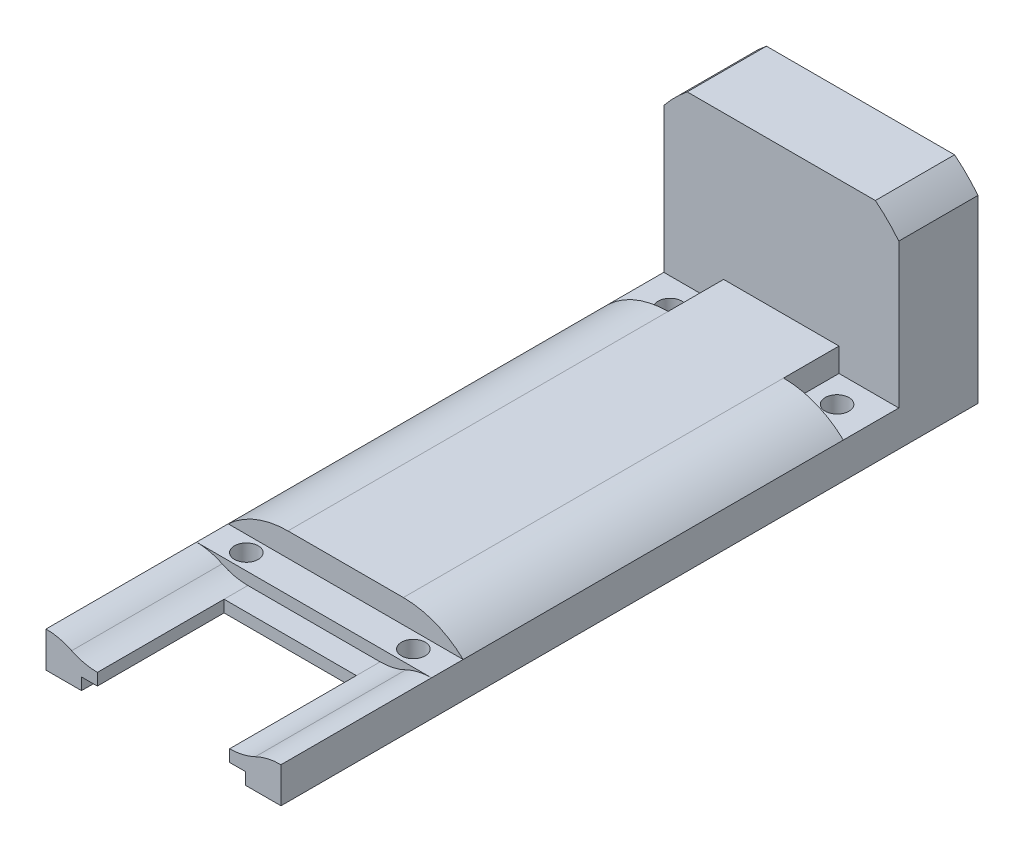
SolidWorks part; units mm, degrees
ref_plane "Front Plane" through (0, 0, 0) normal (0, 0, 1) x (1, 0, 0)
ref_plane "Top Plane" through (0, 0, 0) normal (0, 1, 0) x (1, 0, 0)
ref_plane "Right Plane" through (0, 0, 0) normal (1, 0, 0) x (0, 0, -1)
sketch "Sketch1" plane through (0, 0, 0) normal (0, 0, 1) x (1, 0, 0)
  line L0 (0, 0) -> (0, 29.3495) construction
  line L1 (-14.835, 0) -> (-8.35, 0)
  line L4 (-14.835, 0) -> (-14.835, 4.5)
  line L5 (-14.835, 4.5) -> (-8.35, 4.5)
  line L6 (14.835, 0) -> (14.835, 4.5)
  line L7 (14.835, 0) -> (8.35, 0)
  line L11 (8.35, 4.5) -> (14.835, 4.5)
  line L12 (-8.35, 4.5) -> (8.35, 4.5) construction
  line L13 (-8.35, 0) -> (8.35, 0) construction
  line L14 (-8.35, 0) -> (-8.35, 4.5)
  line L15 (8.35, 0) -> (8.35, 4.5)
  point P10 (0, 21.4888)
  point P13 (0, 23.4888)
  point P16 (0, 0)
  dimension "D1" = 29.67
  dimension "D2" = 6.485
  dimension "D4" = 4.5
extrude "Boss-Extrude1" add sketch "Sketch1" against normal blind 88 contours L14 L5 L4 L1 | L15 L11 L6 L7
sketch "Sketch3" plane through (0, 0, 0) normal (0, 0, 1) x (1, 0, 0)
  line L0 (-14.835, 0) -> (-8.35, 0) construction
  line L1 (-8.35, 0) -> (-10.35, 0)
  line L2 (-8.35, 0) -> (-8.35, 1.5)
  line L3 (-8.35, 1.5) -> (-10.35, 1.5)
  line L4 (-10.35, 0) -> (-10.35, 1.5)
  line L5 (0, 0) -> (0, 11.8528) construction
  line L6 (8.35, 1.5) -> (10.35, 1.5)
  line L7 (10.35, 0) -> (10.35, 1.5)
  line L8 (8.35, 0) -> (10.35, 0)
  line L9 (8.35, 0) -> (8.35, 1.5)
  dimension "D1" = 2
  dimension "D2" = 1.5
extrude "Cut-Extrude2" cut sketch "Sketch3" against normal blind 30
sketch "Sketch4" plane through (0, 0, -88) normal (0, 0, -1) x (-1, 0, 0)
  line L0 (0, 0) -> (0, 13.5394) construction
  line L1 (14.835, 4.5) -> (8.35, 4.5) construction
  line L2 (8.35, 0) -> (8.35, 4.5) construction
  line L3 (8.35, 4.5) -> (10.35, 4.5)
  line L4 (-8.35, 4.5) -> (-8.35, 0)
  line L5 (8.35, 1.5) -> (8.35, 0)
  line L6 (10.35, 1.5) -> (8.35, 1.5)
  line L7 (10.35, 0) -> (10.35, 1.5)
  line L8 (8.35, 0) -> (10.35, 0)
  line L9 (8.35, 4.5) -> (8.35, 0)
  line L11 (10.35, 0) -> (10.35, 4.5)
  line L12 (8.35, 0) -> (10.35, 0)
  line L13 (-8.35, 0) -> (-10.35, 0)
  line L14 (-10.35, 0) -> (-10.35, 4.5)
  line L15 (-8.35, 4.5) -> (-10.35, 4.5)
  dimension "D1" = 0
extrude "Cut-Extrude3" cut sketch "Sketch4" against normal blind 65
sketch "Sketch6" plane through (-10.35, 0, 0) normal (1, 0, 0) x (0, 0, -1)
  line L0 (23, 4.5) -> (0, 4.5) construction
  line L1 (83, 1.5) -> (16, 1.5)
  line L2 (83, 1.5) -> (83, 4.5)
  line L3 (83, 4.5) -> (16, 4.5)
  line L4 (16, 1.5) -> (16, 4.5)
  line L6 (23, 1.5) -> (0, 1.5) construction
  dimension "D1" = 67
extrude "Boss-Extrude2" add sketch "Sketch6" along normal up to surface (20.7 mm away) up to face at (10.35, 2, -37)
sketch "Sketch8" plane through (0, 0, -88) normal (0, 0, -1) x (-1, 0, 0)
  line L0 (-14.835, 0) -> (-14.835, 4.5) construction
  line L3 (-14.835, 0) -> (-14.835, 25.7077)
  line L4 (-14.835, 25.7077) -> (14.835, 25.7077)
  line L6 (-10.35, 1.5) -> (10.35, 1.5) construction
  line L8 (0, 0) -> (0, 41.6063) construction
  line L10 (-10.35, 0) -> (-10.35, 21.2227)
  line L11 (14.835, 0) -> (14.835, 25.7077)
  line L12 (10.35, 0) -> (14.8327, 0)
  line L13 (-14.835, 0) -> (-10.35, 0)
  line L14 (-10.35, 21.2227) -> (10.35, 21.2227)
  line L15 (10.35, 21.2227) -> (10.35, 0)
  arc A1 (14.8327, 22.748) -> (11.874, 25.7067) centre (0, 10.874) ccw construction
  point P26 (0, 25.7077)
  dimension "D1" = 24.2077
  dimension "D2" = 4.485
extrude "Boss-Extrude3" add sketch "Sketch8" against normal blind 5
sketch "Sketch9" plane through (0, 0, -88) normal (0, 0, -1) x (-1, 0, 0)
  line L0 (-15.0091, 25.8817) -> (-15.0091, 22.5273)
  line L7 (-13.437, 24.3096) -> (-15.0091, 25.8817) construction
  line L9 (-15.0091, 25.8817) -> (-11.6546, 25.8817)
  line L10 (-14.835, 25.7077) -> (14.835, 25.7077) construction
  line L11 (0, 0) -> (0, 25.7077) construction
  line L12 (15.0091, 25.8817) -> (15.0091, 22.5273)
  line L13 (15.0091, 25.8817) -> (11.6546, 25.8817)
  arc A1 (-11.6546, 25.8817) -> (-15.0091, 22.5273) centre (-0.0019, 10.8746) ccw
  arc A3 (11.6546, 25.8817) -> (15.0091, 22.5273) centre (0.0019, 10.8746) cw
  dimension "D2" = 19
  dimension "D1" = 45
  dimension "D3" = 3.3544
  dimension "D4" = 0.1741
extrude "Cut-Extrude4" cut sketch "Sketch9" against normal up to surface (5 mm away) up to face at (0, 13.9826, -83)
sketch "Sketch11" plane through (0, 0, -83) normal (0, 0, 1) x (1, 0, 0)
  line L0 (14.835, 4.5) -> (14.835, 22.7481) construction
  line L1 (11.8754, 25.7077) -> (-11.8754, 25.7077) construction
  line L2 (-14.835, 4.5) -> (-14.835, 22.7481) construction
  line L3 (14.835, 4.5) -> (14.835, 22.7481)
  line L4 (11.8754, 25.7077) -> (-11.8754, 25.7077)
  line L5 (-14.835, 4.5) -> (-14.835, 22.7481)
  line L6 (-14.835, 4.5) -> (14.835, 4.5)
  arc A0 (14.835, 22.7481) -> (11.8754, 25.7077) centre (0.0019, 10.8746) ccw construction
  arc A1 (-11.8754, 25.7077) -> (-14.835, 22.7481) centre (-0.0019, 10.8746) ccw construction
  arc A2 (14.835, 22.7481) -> (11.8754, 25.7077) centre (0.0019, 10.8746) ccw
  arc A3 (-11.8754, 25.7077) -> (-14.835, 22.7481) centre (-0.0019, 10.8746) ccw
extrude "Boss-Extrude4" add sketch "Sketch11" along normal blind 5
sketch "Sketch12" plane through (0, 0, -78) normal (0, 0, 1) x (1, 0, 0)
  line L1 (0, 0) -> (0, 30.5664) construction
  line L4 (-14.835, 4.5) -> (-11.835, 7.5)
  line L5 (-11.835, 7.5) -> (11.835, 7.5)
  line L6 (-14.835, 4.5) -> (14.835, 4.5) construction
  line L7 (14.835, 4.5) -> (11.835, 7.5)
  line L8 (-14.835, 4.5) -> (14.835, 4.5)
  line L11 (-14.835, 22.7481) -> (-14.835, 4.5) construction
  point P8 (0, 4.5)
  point P23 (0, 7.5)
  dimension "D1" = 135
  dimension "D2" = 3
extrude "Boss-Extrude5" add sketch "Sketch12" along normal blind 48 from offset 7
sketch "Sketch14" plane through (0, 0, -23) normal (0, 0, 1) x (1, 0, 0)
  line L0 (-11.835, 7.5) -> (-14.835, 4.5) construction
  line L1 (-11.835, 7.5) -> (-14.835, 4.5)
  line L3 (-14.835, 4.5) -> (-8.35, 4.5) construction
  line L5 (0, 0) -> (0, 22.5341) construction
  line L9 (-11.835, 7.5) -> (-10.835, 7.5)
  line L10 (11.835, 7.5) -> (-11.835, 7.5) construction
  line L11 (-10.835, 7.5) -> (-10.835, 4.5)
  line L12 (-14.835, 4.5) -> (-10.835, 4.5)
  line L13 (11.835, 7.5) -> (14.835, 4.5)
  line L14 (11.835, 7.5) -> (10.835, 7.5)
  line L15 (10.835, 7.5) -> (10.835, 4.5)
  line L16 (14.835, 4.5) -> (10.835, 4.5)
  dimension "D1" = 1
extrude "Boss-Extrude6" add sketch "Sketch14" against normal up to surface (48 mm away) up to face at (0, 6, -71)
fillet "Fillet1" radius 11 2 edges at (11.835, 7.5, -47) (-11.835, 7.5, -47)
sketch "Sketch18" plane through (0, 0, -71) normal (0, 0, -1) x (-1, 0, 0)
  line L0 (14.835, 4.5) -> (-14.835, 4.5) construction
  line L1 (-7.2852, 7.5) -> (7.2852, 7.5)
  line L2 (-7.2852, 7.5) -> (-7.2852, 4.5)
  line L3 (-7.2852, 4.5) -> (7.2852, 4.5)
  line L4 (7.2852, 7.5) -> (7.2852, 4.5)
extrude "Boss-Extrude7" add sketch "Sketch18" along normal up to surface (7 mm away) up to face at (0, 17.6792, -78)
sketch "Sketch15" plane through (0, 0, -88) normal (0, 0, -1) x (-1, 0, 0)
  line L7 (-11.85, 1.5) -> (11.85, 1.5)
  line L10 (11.85, 22.7227) -> (11.85, 1.5)
  line L11 (-11.85, 22.7227) -> (11.85, 22.7227)
  line L12 (-11.85, 1.5) -> (-11.85, 22.7227)
  line L13 (11.85, 22.7227) -> (11.85, 1.5)
  line L14 (-11.85, 22.7227) -> (11.85, 22.7227)
  line L15 (-11.85, 1.5) -> (-11.85, 22.7227)
  dimension "D1" = 1.5
extrude "Cut-Extrude6" cut sketch "Sketch15" against normal blind 7
sketch "Sketch16" plane through (0, 0, 0) normal (0, 0, 1) x (1, 0, 0)
  line L0 (-8.35, 1.5) -> (-8.35, 4.5) construction
  line L1 (-14.835, 4.5) -> (-8.35, 4.5) construction
  line L2 (-8.35, 3) -> (8.35, 3) construction
  line L3 (-14.835, 4.5) -> (-8.35, 4.5)
  line L4 (-8.35, 4.5) -> (-8.35, 3)
  line L5 (0, 0) -> (0, 6.6203) construction
  line L6 (8.35, 1.5) -> (8.35, 4.5) construction
  line L7 (14.835, 4.5) -> (8.35, 4.5)
  line L8 (8.35, 4.5) -> (8.35, 3)
  line L9 (8.35, 4.5) -> (-8.35, 4.5) construction
  line L10 (-8.35, 3) -> (8.35, 3)
  line L11 (-8.35, 3) -> (-8.35, 4.5)
  line L12 (-8.35, 4.5) -> (8.35, 4.5)
  line L13 (8.35, 3) -> (8.35, 4.5)
  arc A0 (-14.835, 4.5) -> (-11.5925, 3.75) centre (-14.835, -2.8842) cw
  arc A1 (-11.5925, 3.75) -> (-8.35, 3) centre (-8.35, 10.3842) ccw
  arc A2 (14.835, 4.5) -> (11.5925, 3.75) centre (14.835, -2.8842) ccw
  arc A3 (11.5925, 3.75) -> (8.35, 3) centre (8.35, 10.3842) cw
  point P16 (-11.5925, 4.5)
  dimension "D1" = 1.5
extrude "Cut-Extrude7" cut sketch "Sketch16" against normal blind 19 contours A3 A2 L7 L8 | A1 A0 L3 L4 | L11 L10 L13 L12
sketch "Sketch13" plane through (0, 4.5, 0) normal (0, 1, 0) x (1, 0, 0)
  line L0 (0, 16) -> (0, 78) construction
  line L4 (8.35, 16) -> (-8.35, 16) construction
  line L5 (14.835, 71) -> (14.835, 23) construction
  line L6 (11.8754, 78) -> (-11.8754, 78) construction
  line L9 (-14.835, 47) -> (14.835, 47) construction
  arc A7 (11.874, 75.191) -> (11.874, 73.809) centre (10.5427, 74.5) ccw construction
  arc A8 (-11.874, 73.809) -> (-11.874, 75.191) centre (-10.5427, 74.5) ccw construction
  arc A9 (11.874, 21.691) -> (11.874, 20.309) centre (10.5427, 21) ccw construction
  arc A10 (-11.874, 20.309) -> (-11.874, 21.691) centre (-10.5427, 21) ccw construction
  circle A11 centre (10.5427, 74.5) radius 1.5
  circle A12 centre (-10.5427, 74.5) radius 1.5
  circle A13 centre (10.5427, 21) radius 1.5
  circle A14 centre (-10.5427, 21) radius 1.5
  point P23 (0, 47)
extrude "Cut-Extrude5" cut sketch "Sketch13" against normal through all both and the other way through all
sketch "Sketch17" plane through (0, 1.5, 0) normal (0, -1, 0) x (-1, 0, 0)
  line L1 (7, 26) -> (-7, 26)
  line L2 (7, 26) -> (7, 81)
  line L3 (7, 81) -> (-7, 81)
  line L4 (-7, 26) -> (-7, 81)
  line L8 (11.85, 81) -> (-11.85, 81) construction
  line L10 (-10.35, 81) -> (10.35, 81) construction
  line L11 (14.835, 23) -> (-14.835, 23) construction
  point P14 (0, 81)
  point P15 (0, 81)
  dimension "D1" = 3
  dimension "D3" = 14
extrude "Cut-Extrude8" cut sketch "Sketch17" against normal offset from surface (3 mm away) 3 up to face at (0, 7.5, -57.3333)
